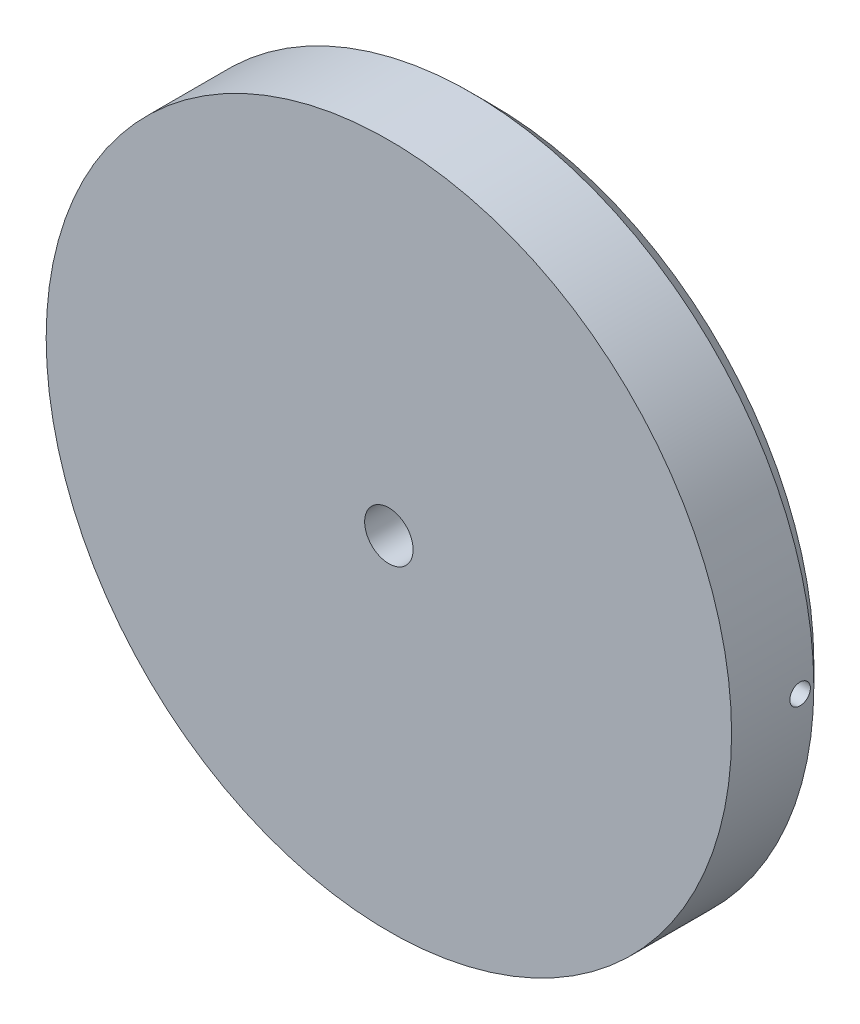
SolidWorks part; units mm, degrees
ref_plane "Front Plane" through (0, 0, 0) normal (0, 0, 1) x (1, 0, 0)
ref_plane "Top Plane" through (0, 0, 0) normal (0, 1, 0) x (1, 0, 0)
ref_plane "Right Plane" through (0, 0, 0) normal (1, 0, 0) x (0, 0, -1)
ref_axis "Z" through (0, 0, 543.0939) along (0, 0, -1)
ref_axis "X" through (17.0818, 0, 0) along (-1, 0, 0)
ref_axis "Y" through (0, 20.242, 0) along (0, -1, 0)
sketch "Sketch1" plane through (0, 0, 0) normal (0, 0, 1) x (1, 0, 0)
  circle A0 centre (0, 0) radius 50
  circle A1 centre (0, 0) radius 3.535
  dimension "D1" = 100
  dimension "D2" = 7.07
extrude "Boss-Extrude1" add sketch "Sketch1" against normal blind 5 and the other way blind 10
sketch "Sketch2" plane through (0, 0, 0) normal (0, 1, 0) x (1, 0, 0)
  line L0 (-16.3173, 0) -> (16.3173, 0) construction
  line L1 (0, -20.5521) -> (0, 20.5521) construction
  circle A0 centre (0, 0) radius 1.5
  dimension "D1" = 3
extrude "Cut-Extrude1" cut sketch "Sketch2" against normal through all
sketch "Sketch3" plane through (0, 0, 0) normal (1, 0, 0) x (0, 0, -1)
  circle A0 centre (0, 0) radius 1.5
  dimension "D1" = 3
extrude "Cut-Extrude2" cut sketch "Sketch3" along normal through all
chamfer "Chamfer1" distance 3 angle 45 1 edges at (50, 0, -5)
sketch "Sketch4" plane through (0, 0, 0) normal (0, 0, 1) x (1, 0, 0)
  circle A0 centre (0, 0) radius 3.535
  circle A2 centre (0, 0) radius 3.535 construction
  circle A3 centre (0, 0) radius 44
  dimension "D1" = 88
extrude "Boss-Extrude2" add sketch "Sketch4" along normal up to surface and the other way up to surface up to face at (50, 0, 10) other way up to face at (47, 0, -5)
sketch "Sketch5" plane through (0, 0, 0) normal (0, 0, 1) x (1, 0, 0)
  line L0 (0, 0) -> (0, -67) construction
  dimension "D1" = 67
ref_plane "Vert" through (0, 0, 0) normal (0.7071, 0.7071, 0) x (0, 0, -1)
equation "\"EyeDiameter\" = 100"
equation "\"BasePlaneDistance\" = \"EyeDiameter\"/2+\"L2Thickness\"+\"EyeClearance\""
equation "\"EyeClearance\" = 2"
equation "\"EyeOD\"= \"EyeDiameter\""
equation "\"D1@Sketch1\"=\"EyeOD\""
equation "\"D2@Sketch1\"= 7.07"
equation "\"pinHoleDiameter\"= 3"
equation "\"D1@Sketch2\"=\"pinHoleDiameter\""
equation "\"D1@Sketch3\"=\"pinHoleDiameter\""
equation "\"D1@Sketch4\"=\"EyeDiameter\"-12"
equation "\"D1@Sketch5\"=\"BasePlaneDistance\""
